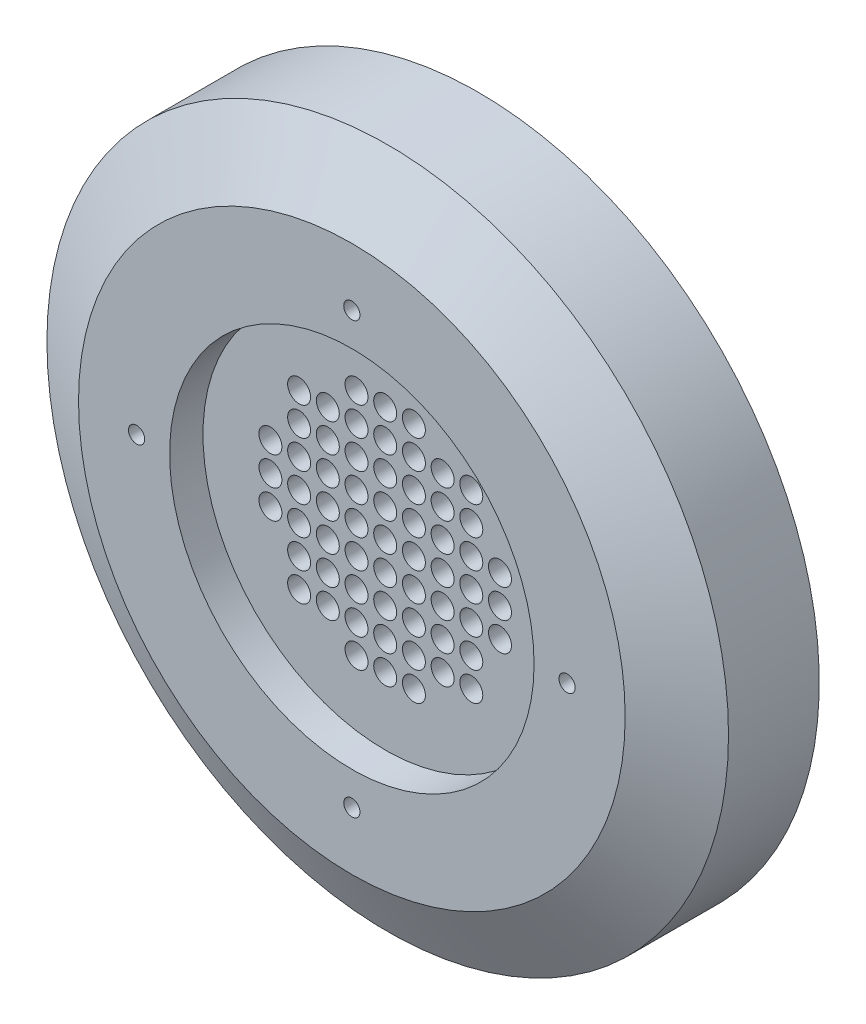
SolidWorks part; units mm, degrees
ref_plane "Plan de face" through (0, 0, 0) normal (0, 0, 1) x (1, 0, 0)
ref_plane "Plan de dessus" through (0, 0, 0) normal (0, 1, 0) x (1, 0, 0)
ref_plane "Plan de droite" through (0, 0, 0) normal (1, 0, 0) x (0, 0, -1)
sketch "Sketch1" plane through (0, 0, 0) normal (0, 0, 1) x (1, 0, 0)
  circle A0 centre (0, 0) radius 47.5
extrude "Boss-Extrude1" add sketch "Sketch1" along normal blind 5
sketch "Sketch2" plane through (0, 0, 5) normal (0, 0, 1) x (1, 0, 0)
  circle A0 centre (0, 0) radius 1.6
extrude "Cut-Extrude1" cut sketch "Sketch2" against normal through all
pattern_linear "LPattern1" count 5 spacing 4 along (0, 1, 0) count 5 spacing 4 along (1, 0, 0) skipping (2, 4), (3, 4), (4, 2), (4, 3), (4, 4) of "Cut-Extrude1"
mirror "Mirror1" about plane through (0, 0, 0) normal (1, 0, 0) of "LPattern1" second plane through (0, 0, 0) second plane normal (0, 1, 0)
sketch "Sketch16" plane through (0, 0, 5) normal (0, 0, 1) x (1, 0, 0)
  circle A0 centre (0, 0) radius 25.4
  circle A1 centre (0, 0) radius 47.5
extrude "Boss-Extrude2" add sketch "Sketch16" along normal blind 4.65
sketch "Sketch17" plane through (0, 0, 0) normal (0, 0, -1) x (-1, 0, 0)
  circle A0 centre (0, 0) radius 42
  circle A1 centre (0, 0) radius 47.5
extrude "Boss-Extrude3" add sketch "Sketch17" along normal blind 8
sketch "Sketch34" plane through (0, 0, 0) normal (0, 0, -1) x (-1, 0, 0)
  line L0 (0, -47.5) -> (0, -30)
  circle A0 centre (0, 0) radius 47.5 construction
hole_wizard "#4-40 Tapped Hole2" positions "Sketch35" profile "Sketch36" tap size "#4-40" standard "ANSI Inch" end condition through all
sketch "Sketch35" plane through (0, 0, 0) normal (0, 0, -1) x (-1, 0, 0)
  point P0 (0, -30)
sketch "Sketch36" plane through (0, -30, 0) normal (1, 0, 0) x (0, 1, 0)
  line L0 (0, 0) -> (0, 9.65)
  line L1 (0, 9.65) -> (1.1303, 9.65)
  line L2 (1.1303, 9.65) -> (1.1303, 0)
  line L5 (1.1303, 0) -> (0, 0)
  line L11 (0, -6.35) -> (0, 107.95) construction
  dimension "Thru Tap Drill Dia." = 2.2606
  dimension "Thru Tap Drill Depth" = 9.65
pattern_circular "CirPattern1" count 4 over 360 about axis through (0, 0, 0) along (0, 0, 1) of "#4-40 Tapped Hole2"
sketch "Sketch39" plane through (0, 0, -8) normal (0, 0, -1) x (-1, 0, 0)
  line L0 (0, -47.5) -> (0, -42)
  circle A0 centre (0, 0) radius 47.5 construction
  circle A1 centre (0, 0) radius 42 construction
hole_wizard "#4-40 Tapped Hole1" positions "Sketch40" profile "Sketch41" tap size "#4-40" standard "ANSI Inch"
sketch "Sketch40" plane through (0, 0, -8) normal (0, 0, -1) x (-1, 0, 0)
  line L0 (0, -47.5) -> (0, -42) construction
  point P0 (0, -44.75)
sketch "Sketch41" plane through (0, -44.75, -8) normal (1, 0, 0) x (0, 1, 0)
  line L0 (0, 0) -> (0, 5.6792)
  line L1 (0, 5.6792) -> (1.1303, 5)
  line L2 (1.1303, 5) -> (1.1303, 0)
  line L5 (1.1303, 0) -> (0, 0)
  line L10 (0, 5.6792) -> (-1.1303, 5) construction
  line L11 (0, -6.35) -> (0, 107.95) construction
  dimension "Tap Drill Dia." = 2.2606
  dimension "Tap Drill Depth" = 5
  dimension "Drill Angle" = 118
pattern_circular "CirPattern2" count 3 over 360 about axis through (0, 0, 0) along (0, 0, 1) of "#4-40 Tapped Hole1"
chamfer "Chamfer1" distance 5 angle 62 1 edges at (47.5, 0, 9.65) first distance on face at (47.5, 0, 9.65)
sketch "Sketch45" plane through (0, 0, 0) normal (1, 0, 0) x (0, 0, -1)
  line L0 (-4.65, 47.5) -> (8, 47.5)
sketch "Sketch46" plane through (0, 0, -8) normal (0, 0, -1) x (-1, 0, 0)
  circle A0 centre (0, 42) radius 1.75
  circle A1 centre (0, 0) radius 42 construction
  circle A2 centre (0, 0) radius 42 construction
extrude "Cut-Extrude2" cut sketch "Sketch46" against normal blind 3
pattern_circular "CirPattern3" count 5 over 360 about axis through (0, 0, -8) along (0, 0, 1) skipping 1, 4 of "Cut-Extrude2" reverse direction yes
hole_wizard "M3x0.5 Tapped Hole1" positions "Sketch56" profile "Sketch57" tap size "M3x0.5" standard "ANSI Metric"
sketch "Sketch56" plane through (0, 0, 0) normal (0, 0, -1) x (-1, 0, 0)
  point P0 (-0.1, -37.2)
sketch "Sketch57" plane through (0.1, -37.2, 0) normal (1, 0, 0) x (0, 1, 0)
  line L0 (0, 0) -> (0, 8.2511)
  line L1 (0, 8.2511) -> (1.25, 7.5)
  line L2 (1.25, 7.5) -> (1.25, 0)
  line L5 (1.25, 0) -> (0, 0)
  line L10 (0, 8.2511) -> (-1.25, 7.5) construction
  line L11 (0, -6.35) -> (0, 107.95) construction
  dimension "Tap Drill Dia." = 2.5
  dimension "Tap Drill Depth" = 7.5
  dimension "Drill Angle" = 118
cosmetic thread "Hole Thread13" parameters "D1"=6, "D2"=3
pattern_circular "CirPattern4" count 4 over 360 about axis through (0, 0, 0) along (0, 0, 1) of "M3x0.5 Tapped Hole1"
cosmetic thread "Hole Thread14" parameters "D1"=6, "D2"=3
cosmetic thread "Hole Thread15" parameters "D1"=6, "D2"=3
cosmetic thread "Hole Thread16" parameters "D1"=6, "D2"=3
